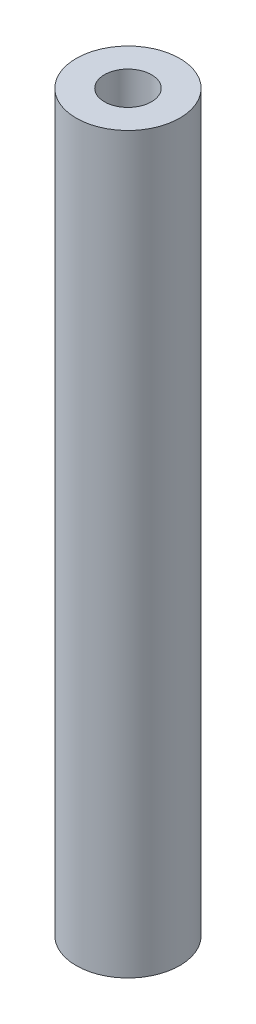
SolidWorks part; units mm, degrees
material "1023 Carbon Steel Sheet (SS)"
ref_plane "Front Plane" through (0, 0, 0) normal (0, 0, 1) x (1, 0, 0)
ref_plane "Top Plane" through (0, 0, 0) normal (0, 1, 0) x (1, 0, 0)
ref_plane "Right Plane" through (0, 0, 0) normal (1, 0, 0) x (0, 0, -1)
sketch "Sketch1" plane through (0, 0, 0) normal (0, 1, 0) x (1, 0, 0)
  circle A0 centre (0, 0) radius 2.5
  circle A1 centre (0, 0) radius 5.5
  dimension "D1" = 3
  dimension "D2" = 5
extrude "Boss-Extrude1" add sketch "Sketch1" along normal blind 78
